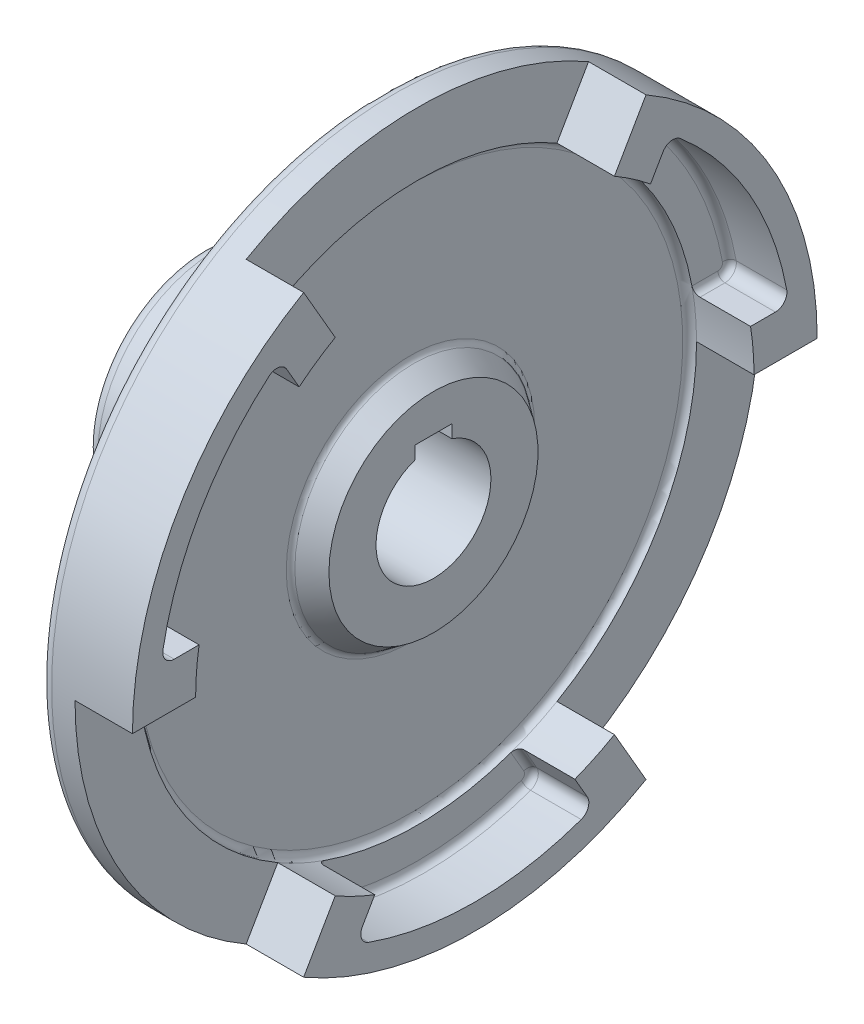
SolidWorks part; units mm, degrees
ref_plane "前基準面" through (0, 0, 0) normal (0, 0, 1) x (1, 0, 0)
ref_plane "上基準面" through (0, 0, 0) normal (0, 1, 0) x (1, 0, 0)
ref_plane "右基準面" through (0, 0, 0) normal (1, 0, 0) x (0, 0, -1)
sketch "草圖1" plane through (0, 0, 0) normal (0, 0, 1) x (1, 0, 0)
  line L0 (0, 0) -> (121.6624, 0) construction
  line L1 (0, 0) -> (0, 51)
  line L2 (0, 51) -> (63, 51)
  line L3 (63, 51) -> (78.5217, 149)
  line L4 (78.5217, 149) -> (93, 149)
  line L5 (93, 149) -> (93, 121.5)
  line L6 (93, 121.5) -> (90, 121.5)
  line L7 (90, 121.5) -> (90, 52.5)
  line L8 (90, 52.5) -> (100, 45.5)
  line L9 (100, 45.5) -> (100, 0)
  line L10 (0, 0) -> (100, 0)
  dimension "D1" = 102
  dimension "D2" = 91
  dimension "D3" = 105
  dimension "D4" = 243
  dimension "D5" = 298
  dimension "D6" = 3
  dimension "D7" = 63
  dimension "D8" = 10
  dimension "D9" = 100
  dimension "D10" = 9
revolve "旋轉1" add sketch "草圖1" angle 360 about L0
sketch "草圖2" plane through (93, 0, 0) normal (1, 0, 0) x (0, 0, -1)
  line L0 (-121.5, 0) -> (-149, 0)
  line L1 (-60.75, 105.2221) -> (-74.5, 129.0378)
  line L2 (-84.7974, 108.8734) -> (-76.4571, 94.4276)
  line L3 (-136.6858, 19) -> (-120.0052, 19)
  circle A0 centre (0, 0) radius 121.5 construction
  arc A1 (-60.75, 105.2221) -> (-76.4571, 94.4276) centre (0, 0) ccw
  arc A3 (-120.0052, 19) -> (-121.5, 0) centre (0, 0) ccw
  circle A4 centre (0, 0) radius 138
  arc A5 (-84.7974, 108.8734) -> (-136.6858, 19) centre (0, 0) ccw
  circle A6 centre (0, 0) radius 149 construction
  arc A7 (-74.5, 129.0378) -> (-149, 0) centre (0, 0) ccw
  dimension "D1" = 60
  dimension "D2" = 19
  dimension "D3" = 19
  dimension "D4" = 11
extrude "伸長1" add sketch "草圖2" along normal blind 25
pattern_circular "環狀複製排列1" count 3 over 360 about axis through (100, 0, 0) along (-1, 0, 0) of "伸長1"
sketch "草圖3" plane through (100, 0, 0) normal (1, 0, 0) x (0, 0, -1)
  line L0 (0, 0) -> (0, 37.9876) construction
  line L1 (8, 23.6854) -> (8, 29.3)
  line L2 (8, 29.3) -> (-8, 29.3)
  line L3 (-8, 23.6854) -> (-8, 29.3)
  arc A0 (-8, 23.6854) -> (8, 23.6854) centre (0, 0) ccw
  point P8 (0, 29.3)
  dimension "D1" = 50
  dimension "D2" = 16
  dimension "D3" = 54.3
extrude "伸長2" cut sketch "草圖3" against normal through all
fillet "圓角1" radius 5 9 edges at (63, 0, 51) (0, 0, 51) (105.5, 108.8734, 84.7974) (105.5, 19, 136.6858) (105.5, -127.8734, 51.8884) (105.5, -127.8734, -51.8884) (105.5, 19, -136.6858) (105.5, 108.8734, -84.7974) (78.5217, 0, 149)
fillet "圓角2" radius 3 2 edges at (90, 0, 52.5) (90, 0, 121.5)
fillet "圓角4" radius 3 15 edges at (93, -118.1091, -46.251) (93, -127.0169, -49.3162) (93, -118.1091, 46.251) (93, -127.0169, 49.3162) (93, 99.1091, -79.16) (93, 106.2176, -85.3417) (93, 19, -125.4109) (93, 20.7993, -134.658) (93, 20.7993, 134.658) (93, 106.2176, 85.3417) (93, -138, 0) (93, 69, -119.5115) (93, 69, 119.5115)
